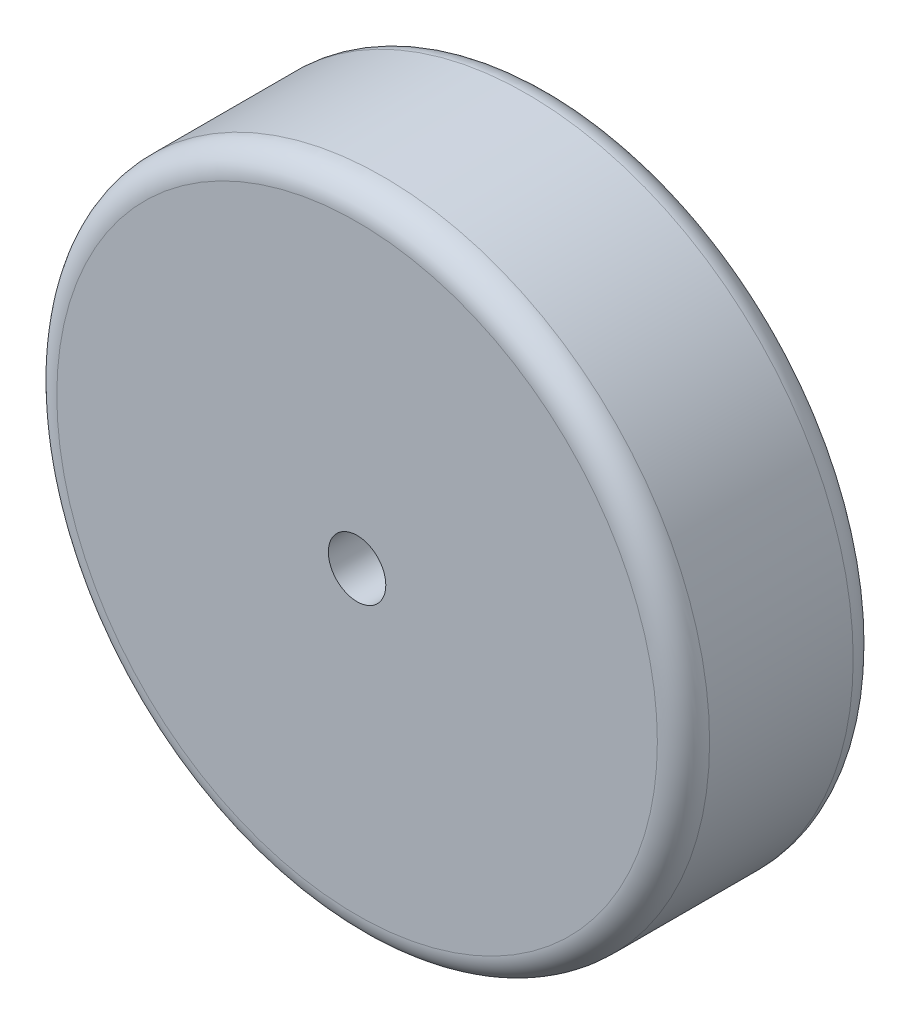
SolidWorks part; units mm, degrees
ref_plane "Front Plane" through (0, 0, 0) normal (0, 0, 1) x (1, 0, 0)
ref_plane "Top Plane" through (0, 0, 0) normal (0, 1, 0) x (1, 0, 0)
ref_plane "Right Plane" through (0, 0, 0) normal (1, 0, 0) x (0, 0, -1)
sketch "Sketch1" plane through (0, 0, 0) normal (0, 0, 1) x (1, 0, 0)
  line L0 (0, 0) -> (0, 25)
  circle A0 centre (0, 0) radius 25
  dimension "D1" = 50
extrude "Boss-Extrude1" add sketch "Sketch1" along normal blind 15 contours A0
fillet "Fillet1" radius 2 2 edges at (25, 0, 15) (25, 0, 0)
sketch "Sketch7" plane through (0, 0, 15) normal (0, 0, 1) x (1, 0, 0)
  circle A0 centre (0, 0) radius 2.2
  dimension "D1" = 4.4
extrude "Cut-Extrude2" cut sketch "Sketch7" against normal through all
ref_plane "Plane1" through (0, 0, 7.5) normal (0, 0, -1) x (-1, 0, 0)
